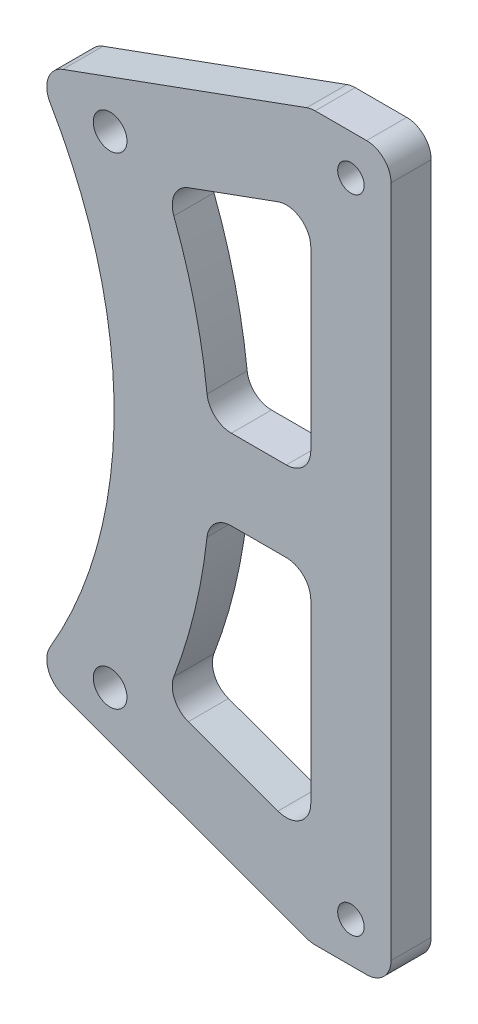
SolidWorks part; units mm, degrees
material "5052-H34"
ref_plane "正面" through (0, 0, 0) normal (0, 0, 1) x (1, 0, 0)
ref_plane "平面" through (0, 0, 0) normal (0, 1, 0) x (1, 0, 0)
ref_plane "右側面" through (0, 0, 0) normal (1, 0, 0) x (0, 0, -1)
sketch "ｽｹｯﾁ1" plane through (0, 0, 0) normal (0, 0, 1) x (1, 0, 0)
  line L0 (0, 0) -> (57.5, 0) construction
  line L1 (-57.5, 30) -> (57.5, 30) construction
  line L2 (-57.5, 30) -> (-57.5, -30) construction
  line L3 (-57.5, -30) -> (57.5, -30) construction
  line L4 (57.5, 30) -> (57.5, -30) construction
  line L5 (-57.5, 30) -> (57.5, -30) construction
  line L6 (-57.5, -30) -> (57.5, 30) construction
  line L7 (92.5, 45) -> (92.5, -45)
  line L8 (92.5, -45) -> (82.5, -45)
  line L9 (82.5, -45) -> (48.0622, -32.4657)
  line L10 (82.5, 45) -> (48.0622, 32.4657)
  line L11 (92.5, 45) -> (82.5, 45)
  circle A0 centre (57.5, 30) radius 2.1
  circle A1 centre (57.5, -30) radius 2.1
  circle A2 centre (87.5, 40) radius 1.65
  circle A3 centre (87.5, -40) radius 1.65
  circle A4 centre (0, 0) radius 58
  point P0 (0, 0)
  dimension "D3" = 4.2
  dimension "D4" = 3.3
  dimension "D7" = 116
  dimension "D1" = 115
  dimension "D2" = 60
  dimension "D5" = 30
  dimension "D6" = 80
  dimension "D8" = 5
  dimension "D9" = 5
  dimension "D10" = 160
  dimension "D11" = 10
extrude "ﾎﾞｽ - 押し出し1" add sketch "ｽｹｯﾁ1" along normal blind 5 contours A4 L9 L8 L7 L11 L10 A0 A1 A2 A3 region at (74.3901, 0, 0)
sketch "ｽｹｯﾁ2" plane through (0, 0, 5) normal (0, 0, 1) x (1, 0, 0)
  line L15 (82.5, 0) -> (70, 0) construction
  line L16 (82.5, 5) -> (70, 5)
  line L17 (82.5, -5) -> (70, -5)
  line L18 (70, 5) -> (69.8212, 5)
  line L19 (70, -5) -> (69.8212, -5)
  line L20 (51.4824, -23.0688) -> (82.5, -34.3582)
  line L21 (82.5, -34.3582) -> (82.5, 34.3582)
  line L22 (82.5, 34.3582) -> (51.4824, 23.0688)
  line L23 (51.4824, -23.0688) -> (82.5, -34.3582)
  line L24 (82.5, -34.3582) -> (82.5, 34.3582)
  line L25 (82.5, 34.3582) -> (51.4824, 23.0688)
  circle A0 centre (0, 0) radius 70
  dimension "D1" = 140
  dimension "D2" = 10
  dimension "D3" = 5
  dimension "D4" = 5
extrude "ｶｯﾄ - 押し出し1" cut sketch "ｽｹｯﾁ2" against normal through all contours A0 L18 L16 L24 L25 | A0 L23 L24 L17 L19 region at (75.2373, 19.0319, 5) region at (75.2373, -19.0319, 5)
fillet "ﾌｨﾚｯﾄ1" radius 3.05 14 edges at (82.5, 45, 2.5) (48.0622, 32.4657, 2.5) (48.0622, -32.4657, 2.5) (82.5, -45, 2.5) (92.5, -45, 2.5) (92.5, 45, 2.5) (82.5, 5, 2.5) (82.5, 34.3582, 2.5) (82.5, -5, 2.5) (82.5, -34.3582, 2.5) (64.2754, -27.725, 2.5) (69.8212, -5, 2.5) (69.8212, 5, 2.5) (64.2754, 27.725, 2.5)
